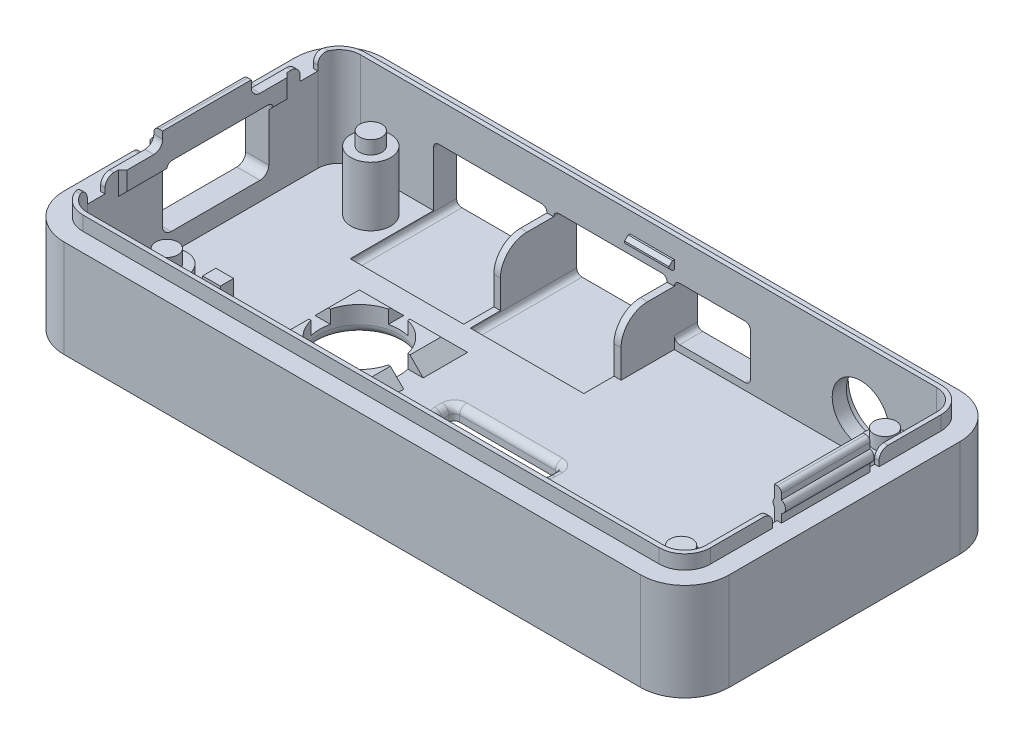
SolidWorks part; units mm, degrees
ref_plane "前视基准面" through (0, 0, 0) normal (0, 0, 1) x (1, 0, 0)
ref_plane "上视基准面" through (0, 0, 0) normal (0, 1, 0) x (1, 0, 0)
ref_plane "右视基准面" through (0, 0, 0) normal (1, 0, 0) x (0, 0, -1)
sketch "zero" plane through (0, 0, 0) normal (0, 1, 0) x (1, 0, 0)
  line L1 (-29.5, 15) -> (29.5, 15)
  line L2 (-32.5, 12) -> (-32.5, -12)
  line L3 (-29.5, -15) -> (29.5, -15)
  line L4 (32.5, 12) -> (32.5, -12)
  line L5 (-32.5, 15) -> (32.5, -15) construction
  line L6 (-32.5, -15) -> (32.5, 15) construction
  line L7 (-25.7, -15) -> (-14.5, -15)
  line L8 (-25.7, -15) -> (-25.7, -9.6569)
  line L9 (-25.7, -9.6569) -> (-14.5, -9.6569)
  line L10 (-14.5, -15) -> (-14.5, -9.6569)
  line L11 (5.2, -15) -> (12.7, -15)
  line L12 (5.2, -15) -> (5.2, -11)
  line L13 (5.2, -11) -> (12.7, -11)
  line L14 (12.7, -15) -> (12.7, -11)
  line L15 (17.8, -15) -> (25.3, -15)
  line L16 (17.8, -15) -> (17.8, -11)
  line L17 (17.8, -11) -> (25.3, -11)
  line L18 (25.3, -15) -> (25.3, -11)
  line L19 (-32.5, 7.7) -> (-19.5, 7.7)
  line L20 (-32.5, 7.7) -> (-32.5, -4.3)
  line L21 (-32.5, -4.3) -> (-19.5, -4.3)
  line L22 (-19.5, 7.7) -> (-19.5, -4.3)
  line L23 (-25.5, 14) -> (25.5, 14)
  line L24 (-25.5, 14) -> (-25.5, 8.8)
  line L25 (-25.5, 8.8) -> (25.5, 8.8)
  line L26 (25.5, 14) -> (25.5, 8.8)
  line L27 (-19.5, 7.2329) -> (-35.5, 7.2329)
  line L28 (-19.5, 7.2329) -> (-19.5, -3.7671)
  line L29 (-19.5, -3.7671) -> (-35.5, -3.7671)
  line L30 (-35.5, 7.2329) -> (-35.5, -3.7671)
  arc A0 (29.5, -15) -> (32.5, -12) centre (29.5, -12) ccw
  arc A1 (29.5, 15) -> (32.5, 12) centre (29.5, 12) cw
  arc A2 (-32.5, -12) -> (-29.5, -15) centre (-29.5, -12) ccw
  arc A3 (-29.5, 15) -> (-32.5, 12) centre (-29.5, 12) ccw
  circle A4 centre (-29, 11.4) radius 3
  circle A5 centre (-29, -11.5) radius 3
  circle A6 centre (29, 11.4) radius 3
  circle A7 centre (29, -11.5) radius 3
  circle A8 centre (-29, 11.4) radius 1.375
  circle A9 centre (-29, -11.5) radius 1.375
  circle A10 centre (29, -11.5) radius 1.375
  circle A11 centre (29, 11.4) radius 1.375
  point P0 (0, 0)
  dimension "D3" = 3
  dimension "D4" = 6
  dimension "D9" = 2.75
  dimension "D1" = 65
  dimension "D2" = 30
  dimension "D5" = 3.6
  dimension "D6" = 3.5
  dimension "D7" = 3.5
  dimension "D8" = 3.5
  dimension "D10" = 12
  dimension "D11" = 7.3
  dimension "D12" = 13
  dimension "D13" = 11.2
  dimension "D14" = 6.8
  dimension "D15" = 19.7
  dimension "D16" = 7.5
  dimension "D17" = 7.5
  dimension "D18" = 5.1
  dimension "D19" = 4
  dimension "D20" = 5.2
  dimension "D21" = 7
  dimension "D22" = 7
  dimension "D23" = 1
  dimension "D24" = 11
  dimension "D25" = 16
sketch "sugar" plane through (0, 0, 0) normal (0, 1, 0) x (1, 0, 0)
  line L1 (-29.5, 15) -> (29.5, 15)
  line L2 (-32.5, 12) -> (-32.5, -12)
  line L3 (-29.5, -15) -> (29.5, -15)
  line L4 (32.5, 12) -> (32.5, -12)
  line L5 (-32.5, 15) -> (32.5, -15) construction
  line L6 (-32.5, -15) -> (32.5, 15) construction
  line L7 (23.5, -11.5) -> (19.5, -11.5)
  line L8 (23.5, -11.5) -> (23.5, -13.9082)
  line L9 (23.5, -13.9082) -> (19.5, -13.9082)
  line L10 (19.5, -11.5) -> (19.5, -13.9082)
  line L11 (16, -11.0071) -> (8.5, -11.0071)
  line L12 (16, -11.0071) -> (16, -15)
  line L13 (16, -15) -> (8.5, -15)
  line L14 (8.5, -11.0071) -> (8.5, -15)
  line L15 (20.5, -13.9082) -> (22.5, -13.9082)
  line L16 (20.5, -13.9082) -> (20.5, -14.8173)
  line L17 (20.5, -14.8173) -> (22.5, -14.8173)
  line L18 (22.5, -13.9082) -> (22.5, -14.8173)
  arc A0 (29.5, 15) -> (32.5, 12) centre (29.5, 12) cw
  arc A1 (29.5, -15) -> (32.5, -12) centre (29.5, -12) ccw
  arc A2 (-32.5, -12) -> (-29.5, -15) centre (-29.5, -12) ccw
  arc A3 (-29.5, 15) -> (-32.5, 12) centre (-29.5, 12) ccw
  circle A4 centre (-29, 11.4) radius 3
  circle A5 centre (-29, 11.4) radius 1.375
  circle A6 centre (-29, -11.5) radius 3
  circle A7 centre (-29, -11.5) radius 1.375
  circle A8 centre (29, 11.4) radius 3
  circle A9 centre (29, 11.4) radius 1.375
  circle A10 centre (29, -11.5) radius 3
  circle A11 centre (29, -11.5) radius 1.375
  dimension "D3" = 3
  dimension "D1" = 65
  dimension "D2" = 30
  dimension "D4" = 9
  dimension "D5" = 4
  dimension "D6" = 3.5
  dimension "D7" = 7.5
  dimension "D8" = 2
  dimension "D9" = 1
sketch "case" plane through (0, 0, 0) normal (0, 1, 0) x (1, 0, 0)
  line L1 (-34.0422, 18) -> (30.9578, 18)
  line L2 (-39.0422, 13) -> (-39.0422, -13)
  line L3 (-34.0422, -18) -> (30.9578, -18)
  line L4 (35.9578, 13) -> (35.9578, -13)
  line L5 (-39.0422, 18) -> (35.9578, -18) construction
  line L6 (-39.0422, -18) -> (35.9578, 18) construction
  arc A0 (-39.0422, -13) -> (-34.0422, -18) centre (-34.0422, -13) ccw
  arc A1 (30.9578, -18) -> (35.9578, -13) centre (30.9578, -13) ccw
  arc A2 (30.9578, 18) -> (35.9578, 13) centre (30.9578, 13) cw
  arc A3 (-34.0422, 18) -> (-39.0422, 13) centre (-34.0422, 13) ccw
  point P0 (-1.5422, 0)
  point P3 (-1.5422, 0)
  dimension "D3" = 5
  dimension "D1" = 75
  dimension "D2" = 36
extrude "凸台-拉伸2" add sketch "case" along normal blind 11
sketch "草图2" plane through (0, 0, 0) normal (0, 1, 0) x (1, 0, 0)
  line L4 (-34.0422, -15.4) -> (30.9578, -15.4)
  line L5 (33.3578, -13) -> (33.3578, 13)
  line L6 (30.9578, 15.4) -> (-34.0422, 15.4)
  line L7 (-36.4422, 13) -> (-36.4422, -13)
  line L8 (33.8578, -13) -> (33.8578, 13)
  line L9 (30.9578, 15.9) -> (-34.0422, 15.9)
  line L10 (-36.9422, 13) -> (-36.9422, -13)
  line L11 (-34.0422, -15.9) -> (30.9578, -15.9)
  line L12 (33.8578, -13) -> (33.8578, 13)
  line L13 (30.9578, 15.9) -> (-34.0422, 15.9)
  line L14 (-36.9422, 13) -> (-36.9422, -13)
  line L15 (-34.0422, -15.9) -> (30.9578, -15.9)
  arc A4 (30.9578, -15.4) -> (33.3578, -13) centre (30.9578, -13) ccw
  arc A5 (33.3578, 13) -> (30.9578, 15.4) centre (30.9578, 13) ccw
  arc A6 (-34.0422, 15.4) -> (-36.4422, 13) centre (-34.0422, 13) ccw
  arc A7 (-36.4422, -13) -> (-34.0422, -15.4) centre (-34.0422, -13) ccw
  arc A8 (30.9578, -15.9) -> (33.8578, -13) centre (30.9578, -13) ccw
  arc A9 (33.8578, 13) -> (30.9578, 15.9) centre (30.9578, 13) ccw
  arc A10 (-34.0422, 15.9) -> (-36.9422, 13) centre (-34.0422, 13) ccw
  arc A11 (-36.9422, -13) -> (-34.0422, -15.9) centre (-34.0422, -13) ccw
  arc A12 (30.9578, -15.9) -> (33.8578, -13) centre (30.9578, -13) ccw
  arc A13 (33.8578, 13) -> (30.9578, 15.9) centre (30.9578, 13) ccw
  arc A14 (-34.0422, 15.9) -> (-36.9422, 13) centre (-34.0422, 13) ccw
  arc A15 (-36.9422, -13) -> (-34.0422, -15.9) centre (-34.0422, -13) ccw
  dimension "D1" = 2.1
  dimension "D2" = 0.5
ref_plane "基准面1" through (0, 11, 0) normal (0, 1, 0) x (1, 0, 0)
sketch "草图3" plane through (0, 11, 0) normal (0, 1, 0) x (1, 0, 0)
  line L4 (-34.0422, -15.4) -> (30.9578, -15.4)
  line L5 (33.3578, -13) -> (33.3578, 13)
  line L6 (30.9578, 15.4) -> (-34.0422, 15.4)
  line L7 (-36.4422, 13) -> (-36.4422, -13)
  line L8 (-34.0422, -15.4) -> (30.9578, -15.4)
  line L9 (33.3578, -13) -> (33.3578, 13)
  line L10 (30.9578, 15.4) -> (-34.0422, 15.4)
  line L11 (-36.4422, 13) -> (-36.4422, -13)
  line L12 (-36.9422, 13) -> (-36.9422, -13)
  line L13 (-34.0422, -15.9) -> (30.9578, -15.9)
  line L14 (33.8578, -13) -> (33.8578, 13)
  line L15 (30.9578, 15.9) -> (-34.0422, 15.9)
  line L16 (-36.9422, 13) -> (-36.9422, -13)
  line L17 (-34.0422, -15.9) -> (30.9578, -15.9)
  line L18 (33.8578, -13) -> (33.8578, 13)
  line L19 (30.9578, 15.9) -> (-34.0422, 15.9)
  arc A4 (30.9578, -15.4) -> (33.3578, -13) centre (30.9578, -13) ccw
  arc A5 (33.3578, 13) -> (30.9578, 15.4) centre (30.9578, 13) ccw
  arc A6 (-34.0422, 15.4) -> (-36.4422, 13) centre (-34.0422, 13) ccw
  arc A7 (-36.4422, -13) -> (-34.0422, -15.4) centre (-34.0422, -13) ccw
  arc A8 (30.9578, -15.4) -> (33.3578, -13) centre (30.9578, -13) ccw
  arc A9 (33.3578, 13) -> (30.9578, 15.4) centre (30.9578, 13) ccw
  arc A10 (-34.0422, 15.4) -> (-36.4422, 13) centre (-34.0422, 13) ccw
  arc A11 (-36.4422, -13) -> (-34.0422, -15.4) centre (-34.0422, -13) ccw
  arc A12 (-36.9422, -13) -> (-34.0422, -15.9) centre (-34.0422, -13) ccw
  arc A13 (30.9578, -15.9) -> (33.8578, -13) centre (30.9578, -13) ccw
  arc A14 (33.8578, 13) -> (30.9578, 15.9) centre (30.9578, 13) ccw
  arc A15 (-34.0422, 15.9) -> (-36.9422, 13) centre (-34.0422, 13) ccw
  arc A16 (-36.9422, -13) -> (-34.0422, -15.9) centre (-34.0422, -13) ccw
  arc A17 (30.9578, -15.9) -> (33.8578, -13) centre (30.9578, -13) ccw
  arc A18 (33.8578, 13) -> (30.9578, 15.9) centre (30.9578, 13) ccw
  arc A19 (-34.0422, 15.9) -> (-36.9422, 13) centre (-34.0422, 13) ccw
  dimension "D1" = 0
  dimension "D2" = 0
extrude "凸台-拉伸4" add sketch "草图3" along normal blind 1.6
sketch "草图5" plane through (0, 11, 0) normal (0, 1, 0) x (1, 0, 0)
  line L0 (33.3578, -13) -> (33.3578, 13) construction
  line L1 (33.0578, 5) -> (33.3578, 5)
  line L2 (33.0578, 5) -> (33.0578, -5)
  line L3 (33.0578, -5) -> (33.3578, -5)
  line L4 (33.3578, 5) -> (33.3578, -5)
  line L5 (33.0578, 5) -> (33.3578, -5) construction
  line L6 (33.0578, -5) -> (33.3578, 5) construction
  point P0 (33.2078, 0)
  dimension "D2" = 10
  dimension "D3" = 0.3
  dimension "D4" = 0
ref_plane "基准面3" through (33.8578, 0, 0) normal (1, 0, 0) x (0, 0, -1)
ref_plane "基准面7" through (-36.9422, 0, 0) normal (-1, 0, 0) x (0, 0, 1)
ref_plane "基准面8" through (0, 0, 0) normal (0, -1, 0) x (-1, 0, 0)
sketch "草图14" plane through (0, 11, 0) normal (0, 1, 0) x (1, 0, 0)
  line L4 (-34.0422, -15.4) -> (30.9578, -15.4)
  line L5 (33.3578, -13) -> (33.3578, 13)
  line L6 (30.9578, 15.4) -> (-34.0422, 15.4)
  line L7 (-36.4422, 13) -> (-36.4422, -13)
  line L8 (-34.0422, -15.4) -> (30.9578, -15.4)
  line L9 (33.3578, -13) -> (33.3578, 13)
  line L10 (30.9578, 15.4) -> (-34.0422, 15.4)
  line L11 (-36.4422, 13) -> (-36.4422, -13)
  arc A4 (30.9578, -15.4) -> (33.3578, -13) centre (30.9578, -13) ccw
  arc A5 (33.3578, 13) -> (30.9578, 15.4) centre (30.9578, 13) ccw
  arc A6 (-34.0422, 15.4) -> (-36.4422, 13) centre (-34.0422, 13) ccw
  arc A7 (-36.4422, -13) -> (-34.0422, -15.4) centre (-34.0422, -13) ccw
  arc A8 (30.9578, -15.4) -> (33.3578, -13) centre (30.9578, -13) ccw
  arc A9 (33.3578, 13) -> (30.9578, 15.4) centre (30.9578, 13) ccw
  arc A10 (-34.0422, 15.4) -> (-36.4422, 13) centre (-34.0422, 13) ccw
  arc A11 (-36.4422, -13) -> (-34.0422, -15.4) centre (-34.0422, -13) ccw
  dimension "D1" = 0
extrude "切除-拉伸2" cut sketch "草图14" against normal blind 9.5
extrude "凸台-拉伸12" add sketch "草图5" against normal blind 2 and the other way blind 1.6
sketch "草图15" plane through (0, 1.5, 0) normal (0, 1, 0) x (1, 0, 0)
  line L1 (35.9578, -13) -> (35.9578, 13) construction
  line L5 (-39.0422, 13) -> (-39.0422, -13) construction
  line L6 (-34.0422, -18) -> (30.9578, -18) construction
  line L7 (30.9578, 18) -> (-34.0422, 18) construction
  circle A0 centre (29.0603, -11.5295) radius 2.25
  circle A1 centre (-28.9397, -11.5295) radius 2.25
  circle A2 centre (29.0603, 11.4705) radius 2.25
  circle A3 centre (-28.9397, 11.4705) radius 2.25
  dimension "D1" = 4.5
  dimension "D2" = 6.8975
  dimension "D3" = 10.1025
  dimension "D4" = 6.4705
  dimension "D5" = 6.5295
extrude "凸台-拉伸13" add sketch "草图15" along normal blind 6.7
sketch "草图16" plane through (0, 8.2, 0) normal (0, 1, 0) x (1, 0, 0)
  circle A0 centre (29.0603, -11.5295) radius 1.25
  circle A1 centre (29.0603, 11.4705) radius 1.25
  circle A2 centre (-28.9397, -11.5295) radius 1.25
  circle A3 centre (-28.9397, 11.4705) radius 1.25
  dimension "D1" = 2.5
extrude "凸台-拉伸14" add sketch "草图16" along normal blind 1.5
sketch "草图17" plane through (0, 12.6, 0) normal (0, 1, 0) x (1, 0, 0)
  line L0 (33.3578, -13) -> (33.3578, -5) construction
  line L1 (33.3578, -5) -> (33.8578, -5)
  line L2 (33.3578, -5) -> (33.3578, -6)
  line L3 (33.3578, -6) -> (33.8578, -6)
  line L4 (33.8578, -5) -> (33.8578, -6)
  line L5 (33.3578, -13) -> (33.3578, 13) construction
  line L6 (33.8578, -13) -> (33.8578, 13) construction
  line L8 (33.3578, 5) -> (33.8578, 5)
  line L9 (33.3578, 5) -> (33.3578, 6)
  line L10 (33.3578, 6) -> (33.8578, 6)
  line L11 (33.8578, 5) -> (33.8578, 6)
  dimension "D1" = 1
  dimension "D2" = 1
extrude "切除-拉伸3" cut sketch "草图17" against normal blind 1.6
sketch "草图19" plane through (0, 12.6, 0) normal (0, 1, 0) x (1, 0, 0)
  line L0 (33.0578, 5) -> (33.0578, -5) construction
  line L1 (33.8578, -5) -> (33.0578, -5)
  line L2 (33.8578, -5) -> (33.8578, 5)
  line L3 (33.8578, 5) -> (33.0578, 5)
  line L4 (33.0578, -5) -> (33.0578, 5)
extrude "凸台-拉伸15" add sketch "草图19" along normal blind 1.8
sketch "草图20" plane through (0, 0, -5) normal (0, 0, -1) x (-1, 0, 0)
  line L0 (-30.9578, 11) -> (-35.9578, 11) construction
  line L3 (-33.8578, 11) -> (-33.8578, 14.4) construction
  circle A0 centre (-33.6078, 12.6) radius 0.7
  dimension "D1" = 1.4
  dimension "D2" = 1.6
  dimension "D3" = 0.25
extrude "凸台-拉伸16" add sketch "草图20" against normal blind 10
fillet "圆角4" radius 0.5 1 edges at (33.8578, 14.4, 0)
sketch "草图37" plane through (0, 0, -15.4) normal (0, 0, 1) x (1, 0, 0)
  line L0 (-34.0422, 12.6) -> (30.9578, 12.6) construction
  line L1 (-3.6422, 10.3) -> (1.3578, 10.3)
  line L2 (-3.6422, 10.3) -> (-3.6422, 9.3)
  line L3 (-3.6422, 9.3) -> (1.3578, 9.3)
  line L4 (1.3578, 10.3) -> (1.3578, 9.3)
  line L5 (33.3578, 12.6) -> (33.3578, 1.5) construction
  dimension "D1" = 5
  dimension "D2" = 1
  dimension "D3" = 2.3
  dimension "D4" = 32
extrude "凸台-拉伸17" add sketch "草图37" along normal blind 0.6
chamfer "倒角1" distance 0.4 angle 45 2 edges at (-1.1422, 9.3, -14.8) (-1.1422, 10.3, -14.8)
sketch "草图38" plane through (0, 0, 15.4) normal (0, 0, -1) x (-1, 0, 0)
  line L0 (-30.9578, 12.6) -> (34.0422, 12.6) construction
  line L1 (4.5422, 10.4) -> (-1.4578, 10.4)
  line L2 (4.5422, 10.4) -> (4.5422, 9.4)
  line L3 (4.5422, 9.4) -> (-1.4578, 9.4)
  line L4 (-1.4578, 10.4) -> (-1.4578, 9.4)
  point P6 (1.5422, 10.4)
  point P7 (1.5422, 12.6)
  dimension "D1" = 1
  dimension "D2" = 6
  dimension "D3" = 2.2
extrude "凸台-拉伸18" add sketch "草图38" along normal blind 0.7
chamfer "倒角2" distance 0.4 angle 45 2 edges at (-1.5422, 9.4, 14.7) (-1.5422, 10.4, 14.7)
sketch "草图39" plane through (0, 0, -18) normal (0, 0, -1) x (-1, 0, 0)
  line L0 (-30.9578, 0) -> (34.0422, 0) construction
  line L1 (-35.9578, 11) -> (-35.9578, 0) construction
  circle A0 centre (-22.3721, 5.7789) radius 4
  dimension "D1" = 5.7789
  dimension "D3" = 8
  dimension "D2" = 13.5857
extrude "切除-拉伸4" cut sketch "草图39" against normal blind 1
sketch "草图41" plane through (0, 0, -18) normal (0, 0, -1) x (-1, 0, 0)
  line L0 (-30.9578, 0) -> (34.0422, 0) construction
  line L1 (-9.9578, 2.2789) -> (-1.3578, 2.2789)
  line L2 (-9.9578, 2.2789) -> (-9.9578, 8.2789)
  line L3 (-9.9578, 8.2789) -> (-1.3578, 8.2789)
  line L4 (-1.3578, 2.2789) -> (-1.3578, 8.2789)
  line L5 (-0.5578, 0.7789) -> (12.2422, 0.7789)
  line L6 (-0.5578, 0.7789) -> (-0.5578, 8.2789)
  line L7 (-0.5578, 8.2789) -> (12.2422, 8.2789)
  line L8 (12.2422, 0.7789) -> (12.2422, 8.2789)
  line L9 (12.9922, 0.7789) -> (25.7922, 0.7789)
  line L10 (12.9922, 0.7789) -> (12.9922, 8.2789)
  line L11 (12.9922, 8.2789) -> (25.7922, 8.2789)
  line L12 (25.7922, 0.7789) -> (25.7922, 8.2789)
  line L13 (-35.9578, 11) -> (-35.9578, 0) construction
  point P14 (0, 0)
  point P15 (0, 0)
  dimension "D1" = 8.2789
  dimension "D2" = 26
  dimension "D3" = 8.6
  dimension "D4" = 6
  dimension "D5" = 0.8
  dimension "D6" = 7.5
  dimension "D7" = 12.8
  dimension "D8" = 0.75
  dimension "D9" = 12.8
extrude "切除-拉伸5" cut sketch "草图41" against normal blind 12
fillet "圆角5" radius 0.6 14 edges at (-19.3922, 0.7789, -6) (-5.8422, 0.7789, -6) (1.3578, 2.2789, -16.7) (9.9578, 2.2789, -16.7) (9.9578, 8.2789, -16.7) (1.3578, 8.2789, -16.7) (0.5578, 8.2789, -16.7) (-12.2422, 8.2789, -16.7) (-12.9922, 8.2789, -16.7) (-25.7922, 8.2789, -16.7) (-12.2422, 0.7789, -12) (0.5578, 0.7789, -12) (-12.9922, 0.7789, -12) (-25.7922, 0.7789, -12)
sketch "草图42" plane through (0, 0, -17) normal (0, 0, -1) x (-1, 0, 0)
  circle A0 centre (-22.3721, 5.7789) radius 3.2
extrude "切除-拉伸6" cut sketch "草图42" against normal blind 1.6
sketch "草图44" plane through (-39.0422, 0, 0) normal (-1, 0, 0) x (0, 0, 1)
  line L0 (-18, 11) -> (-18, 0) construction
  line L1 (-7.4705, 3.6) -> (4.5295, 3.6)
  line L2 (-7.4705, 3.6) -> (-7.4705, 11)
  line L3 (-7.4705, 11) -> (4.5295, 11)
  line L4 (4.5295, 3.6) -> (4.5295, 11)
  line L5 (-7.4705, 3.6) -> (4.5295, 11) construction
  line L6 (-7.4705, 11) -> (4.5295, 3.6) construction
  line L7 (-13, 0) -> (13, 0) construction
  point P0 (-1.4705, 7.3)
  dimension "D1" = 12
  dimension "D2" = 16.5295
  dimension "D3" = 7.3
  dimension "D4" = 7.4
extrude "切除-拉伸8" cut sketch "草图44" against normal up to next
sketch "草图46" plane through (-36.4422, 0, 0) normal (1, 0, 0) x (0, 0, -1)
  line L0 (13, 12.6) -> (-13, 12.6) construction
  line L1 (-10, 12.6) -> (10, 12.6)
  line L2 (-10, 12.6) -> (-10, 11)
  line L3 (-10, 11) -> (10, 11)
  line L4 (10, 12.6) -> (10, 11)
  line L6 (-18, 11) -> (-18, 0) construction
  point P10 (0, 0)
  dimension "D1" = 8
  dimension "D2" = 8
extrude "凸台-拉伸19" add sketch "草图46" along normal blind 0.5
chamfer "倒角3" distance 1 angle 45 2 edges at (-35.9422, 11.8, -10) (-35.9422, 11.8, 10)
chamfer "倒角4" distance 1 angle 45 2 edges at (-36.4422, 11, -8.4853) (-36.4422, 11, 7.0147)
fillet "圆角7" radius 1 2 edges at (-37.7422, 3.6, 4.5295) (-37.7422, 3.6, -7.4705)
sketch "草图47" plane through (0, 0, -15.4) normal (0, 0, 1) x (1, 0, 0)
  line L1 (-12.9922, 1.5) -> (-12.2422, 1.5)
  line L2 (-12.9922, 1.5) -> (-12.9922, 7.6789)
  line L3 (-12.9922, 7.6789) -> (-12.2422, 7.6789)
  line L4 (-12.2422, 1.5) -> (-12.2422, 7.6789)
  line L5 (0.5578, 1.5) -> (1.3578, 1.5)
  line L6 (0.5578, 1.5) -> (0.5578, 7.6789)
  line L7 (0.5578, 7.6789) -> (1.3578, 7.6789)
  line L8 (1.3578, 1.5) -> (1.3578, 7.6789)
extrude "凸台-拉伸20" add sketch "草图47" along normal blind 6
fillet "圆角8" radius 3 2 edges at (0.9578, 7.6789, -9.4) (-12.6172, 7.6789, -9.4)
sketch "草图48" plane through (0, 12.6, 0) normal (0, 1, 0) x (1, 0, 0)
  line L0 (-35.9422, 9) -> (-35.9422, -9) construction
  line L1 (-35.9422, -5) -> (-36.9422, -5)
  line L2 (-35.9422, -5) -> (-35.9422, 5)
  line L3 (-35.9422, 5) -> (-36.9422, 5)
  line L4 (-36.9422, -5) -> (-36.9422, 5)
  line L5 (-36.9422, 13) -> (-36.9422, -13) construction
  point P8 (0, 0)
  point P10 (0, 0)
  point P11 (0, 0)
  point P13 (0, 0)
extrude "凸台-拉伸21" add sketch "草图48" along normal blind 1.8
sketch "草图49" plane through (0, 0, 5) normal (0, 0, 1) x (1, 0, 0)
  line L0 (-34.0422, 11) -> (-39.0422, 11) construction
  line L1 (-36.9422, 14.4) -> (-36.9422, 12.6) construction
  circle A0 centre (-36.6922, 12.6) radius 0.7
  dimension "D1" = 1.4
  dimension "D2" = 1.6
  dimension "D3" = 0.25
extrude "凸台-拉伸22" add sketch "草图49" against normal blind 10
sketch "草图50" plane through (0, 12.6, 0) normal (0, 1, 0) x (1, 0, 0)
  line L0 (-36.4422, 13) -> (-36.4422, 9.5) construction
  line L1 (-36.4422, 13) -> (-36.9422, 13)
  line L2 (-36.4422, 13) -> (-36.4422, 11)
  line L3 (-36.4422, 11) -> (-36.9422, 11)
  line L4 (-36.9422, 13) -> (-36.9422, 11)
  line L5 (-36.9422, 13) -> (-36.9422, 5) construction
  line L6 (-36.4422, -9.5) -> (-36.4422, -13) construction
  line L7 (-36.4422, -11) -> (-36.9422, -11)
  line L8 (-36.4422, -11) -> (-36.4422, -13)
  line L9 (-36.4422, -13) -> (-36.9422, -13)
  line L10 (-36.9422, -11) -> (-36.9422, -13)
  line L11 (-36.9422, -5) -> (-36.9422, -13) construction
  line L12 (30.9578, 18) -> (-34.0422, 18) construction
  line L13 (-34.0422, -18) -> (30.9578, -18) construction
  dimension "D1" = 2
  dimension "D2" = 2
  dimension "D3" = 5
  dimension "D4" = 5
extrude "切除-拉伸10" cut sketch "草图50" against normal blind 1.6
fillet "圆角9" radius 1 6 edges at (33.6078, 12.6, 6) (33.6078, 12.6, -6) (-36.6922, 12.6, -13) (-36.6922, 12.6, -11) (-36.6922, 12.6, 11) (-36.6922, 12.6, 13)
fillet "圆角10" radius 0.6 1 edges at (-36.9422, 14.4, 0)
fillet "圆角11" radius 0.6 2 edges at (-36.4422, 11, -7.4705) (-36.4422, 11, 4.5295)
fillet "圆角12" radius 0.6 2 edges at (-37.9922, 11, 4.5295) (-37.9922, 11, -7.4705)
sketch "草图51" plane through (0, 0, 0) normal (0, -1, 0) x (1, 0, 0)
  line L0 (35.9578, 13) -> (35.9578, -13) construction
  line L1 (6.2578, 2.3) -> (-5.7422, 2.3)
  line L2 (6.2578, 2.3) -> (6.2578, 4.3)
  line L3 (6.2578, 4.3) -> (-5.7422, 4.3)
  line L4 (-5.7422, 2.3) -> (-5.7422, 4.3)
  line L5 (30.9578, -18) -> (-34.0422, -18) construction
  dimension "D1" = 2
  dimension "D2" = 12
  dimension "D3" = 29.7
  dimension "D4" = 20.3
extrude "切除-拉伸11" cut sketch "草图51" against normal blind 1.5
fillet "圆角13" radius 0.6 4 edges at (-5.7422, 0.75, 4.3) (-5.7422, 0.75, 2.3) (6.2578, 0.75, 4.3) (6.2578, 0.75, 2.3)
sketch "草图52" plane through (0, 1.5, 0) normal (0, 1, 0) x (1, 0, 0)
  line L0 (-11.5279, -7.2295) -> (-20.7279, -7.2295)
  line L5 (-20.7279, -7.2295) -> (-20.7279, 1.9705)
  line L6 (-11.5279, 1.9705) -> (-20.7279, 1.9705)
  line L7 (-11.5279, -7.2295) -> (-11.5279, 1.9705)
  line L8 (-39.0422, -5.1295) -> (-39.0422, -13) construction
  line L9 (-34.0422, -18) -> (30.9578, -18) construction
  point P6 (0, 0)
  point P7 (0, 0)
  point P8 (0, 0)
  point P9 (0, 0)
  point P10 (0, 0)
  dimension "D1" = 9.2
  dimension "D2" = 9.2
  dimension "D3" = 18.3143
  dimension "D4" = 10.7705
extrude "凸台-拉伸23" add sketch "草图52" along normal blind 1.5
chamfer "倒角5" distance 1.5 angle 45 4 edges at (-16.1279, 1.5, -1.9705) (-11.5279, 1.5, 2.6295) (-16.1279, 1.5, 7.2295) (-20.7279, 1.5, 2.6295)
sketch "草图53" plane through (0, 0, 0) normal (0, -1, 0) x (1, 0, 0)
  line L1 (30.9578, -18) -> (-34.0422, -18) construction
  line L2 (-39.0422, -13) -> (-39.0422, 13) construction
  circle A0 centre (-16.1279, 2.6295) radius 4.5
  point P4 (0, 0)
  dimension "D1" = 9
  dimension "D2" = 20.6295
  dimension "D3" = 22.9143
extrude "切除-拉伸12" cut sketch "草图53" against normal up to next
fillet "圆角14" radius 1 1 edges at (-16.1279, 0, -1.8705)
sketch "草图55" plane through (0, 3, 0) normal (0, 1, 0) x (1, 0, 0)
  line L1 (-10.0279, -3.7295) -> (-22.2279, -3.7295)
  line L2 (-10.0279, -3.7295) -> (-10.0279, -1.5295)
  line L3 (-10.0279, -1.5295) -> (-22.2279, -1.5295)
  line L4 (-22.2279, -3.7295) -> (-22.2279, -1.5295)
  line L5 (-10.0279, -3.7295) -> (-22.2279, -1.5295) construction
  line L6 (-10.0279, -1.5295) -> (-22.2279, -3.7295) construction
  circle A0 centre (-16.1279, -2.6295) radius 4.5 construction
  point P0 (-16.1279, -2.6295)
  point P5 (0, 0)
  dimension "D1" = 12.2
  dimension "D2" = 2.2
extrude "切除-拉伸13" cut sketch "草图55" against normal blind 1.5
sketch "草图56" plane through (0, 3, 0) normal (0, 1, 0) x (1, 0, 0)
  line L1 (-15.0279, -8.7295) -> (-17.2279, -8.7295)
  line L2 (-15.0279, -8.7295) -> (-15.0279, 3.4705)
  line L3 (-15.0279, 3.4705) -> (-17.2279, 3.4705)
  line L4 (-17.2279, -8.7295) -> (-17.2279, 3.4705)
  line L5 (-15.0279, -8.7295) -> (-17.2279, 3.4705) construction
  line L6 (-15.0279, 3.4705) -> (-17.2279, -8.7295) construction
  arc A0 (-11.7644, -3.7295) -> (-11.7644, -1.5295) centre (-16.1279, -2.6295) ccw construction
  point P0 (-16.1279, -2.6295)
  point P5 (0, 0)
  point P6 (0, 0)
  point P7 (0, 0)
  dimension "D1" = 12.2
  dimension "D2" = 2.2
extrude "切除-拉伸14" cut sketch "草图56" against normal blind 1.5
sketch "草图62" plane through (0, 0, 0) normal (0, -1, 0) x (1, 0, 0)
  line L54 (24.7651, -13.4168) -> (25.178, -13.6486)
  line L55 (25.178, -13.6486) -> (27.3204, -14.8522)
  line L56 (27.3204, -14.8522) -> (27.7334, -15.0868)
  line L57 (28.5939, -15.077) -> (29.0014, -14.8329)
  line L58 (29.0014, -14.8329) -> (31.1156, -13.5806)
  line L60 (31.1156, -13.5806) -> (31.5232, -13.3394)
  line L61 (31.9449, -12.5909) -> (31.9059, -9.1833)
  line L62 (31.4672, -8.4446) -> (31.0542, -8.2128)
  line L63 (31.0542, -8.2128) -> (28.9118, -7.0092)
  line L65 (28.9118, -7.0092) -> (28.4988, -6.7746)
  line L66 (27.6383, -6.7844) -> (27.2308, -7.0284)
  line L67 (27.2308, -7.0284) -> (25.1166, -8.2808)
  line L68 (25.1166, -8.2808) -> (24.709, -8.522)
  line L69 (24.2873, -9.2705) -> (24.3263, -12.6781)
  line L70 (30.9723, -13.0066) -> (28.3571, -14.5582)
  line L73 (27.9554, -14.5628) -> (25.3196, -13.0685)
  line L74 (25.3127, -12.7181) -> (27.8396, -11.1675)
  line L75 (27.0208, -8.5981) -> (27.3152, -8.4295)
  line L76 (27.3432, -8.3807) -> (27.3334, -7.5259)
  line L77 (27.3613, -7.4772) -> (27.9105, -7.1575)
  line L78 (27.9937, -7.2049) -> (28.0239, -9.8432)
  line L79 (27.996, -9.892) -> (27.0618, -10.4356)
  line L80 (25.0712, -8.7971) -> (25.6147, -8.4803)
  line L81 (25.6979, -8.5278) -> (25.7123, -9.7842)
  line L82 (25.6843, -9.833) -> (25.1408, -10.147)
  line L83 (25.0576, -10.0995) -> (25.0433, -8.8459)
  line L84 (27.0608, -9.1049) -> (27.3214, -8.9708)
  line L85 (27.3506, -9.0303) -> (27.3583, -9.7027)
  line L86 (27.3304, -9.7514) -> (27.0869, -9.891)
  line L129 (27.3214, -8.9708) -> (27.3152, -8.4295)
  line L130 (27.3506, -9.0303) -> (27.3432, -8.3807)
  spline S0 degree 3 poles (27.7334, -15.0868) (27.8682, -15.1594) (28.0168, -15.1976) (28.1649, -15.1959) knots 3 3 3 3 4 4 4 4
  spline S1 degree 3 poles (28.1649, -15.1959) (28.3131, -15.1942) (28.4608, -15.1526) (28.5939, -15.077) knots 4 4 4 4 5 5 5 5
  spline S2 degree 3 poles (31.5232, -13.3394) (31.7864, -13.1825) (31.9484, -12.8957) (31.9449, -12.5909) knots 8 8 8 8 9 9 9 9
  spline S3 degree 3 poles (31.9059, -9.1833) (31.9024, -8.8756) (31.7339, -8.5954) (31.4672, -8.4446) knots 10 10 10 10 11 11 11 11
  spline S4 degree 3 poles (28.4988, -6.7746) (28.364, -6.6992) (28.2154, -6.6638) (28.0673, -6.6655) knots 14 14 14 14 15 15 15 15
  spline S5 degree 3 poles (28.0673, -6.6655) (27.9191, -6.6672) (27.7714, -6.706) (27.6383, -6.7844) knots 15 15 15 15 16 16 16 16
  spline S6 degree 3 poles (24.709, -8.522) (24.4429, -8.6789) (24.2838, -8.9628) (24.2873, -9.2705) knots 19 19 19 19 20 20 20 20
  spline S7 degree 3 poles (24.3263, -12.6781) (24.3298, -12.983) (24.4955, -13.266) (24.7651, -13.4168) knots 21 21 21 21 22 22 22 22
  spline S8 degree 2 poles (28.3952, -11.1612) (30.9878, -12.6189) (30.9935, -12.6217) knots 0 0 0 1 1 1
  spline S9 degree 3 poles (30.9935, -12.6217) (31.1285, -12.717) (31.1167, -12.9223) (30.9723, -13.0066) knots 1 1 1 1 2 2 2 2
  spline S10 degree 3 poles (28.3571, -14.5582) (28.2354, -14.6309) (28.0815, -14.6326) (27.9554, -14.5628) knots 3 3 3 3 4 4 4 4
  spline S11 degree 3 poles (25.3196, -13.0685) (25.1848, -12.9931) (25.1797, -12.7994) (25.3127, -12.7181) knots 5 5 5 5 6 6 6 6
  spline S12 degree 3 poles (27.8396, -11.1675) (28.0094, -11.0658) (28.2231, -11.0634) (28.3952, -11.1612) knots 7 7 7 7 8 8 8 8
  spline S13 degree 3 poles (27.3334, -7.5259) (27.3332, -7.506) (27.3415, -7.4888) (27.3613, -7.4772) knots 3 3 3 3 4 4 4 4
  spline S14 degree 3 poles (27.9105, -7.1575) (27.9473, -7.1371) (27.9932, -7.1622) (27.9937, -7.2049) knots 5 5 5 5 6 6 6 6
  spline S15 degree 3 poles (28.0239, -9.8432) (28.0241, -9.8632) (28.0158, -9.8832) (27.996, -9.892) knots 7 7 7 7 8 8 8 8
  spline S16 degree 3 poles (27.0618, -10.4356) (26.456, -10.7873) (25.9526, -10.8614) (25.9447, -10.1776) knots 9 9 9 9 10 10 10 10
  spline S17 degree 3 poles (25.9447, -10.1776) (25.9372, -9.5195) (26.4405, -8.9353) (27.0208, -8.5981) knots 10 10 10 10 11 11 11 11
  spline S18 degree 3 poles (25.0433, -8.8459) (25.043, -8.8259) (25.0542, -8.8058) (25.0712, -8.7971) knots 0 0 0 0 1 1 1 1
  spline S19 degree 3 poles (25.6147, -8.4803) (25.6515, -8.4599) (25.6974, -8.485) (25.6979, -8.5278) knots 2 2 2 2 3 3 3 3
  spline S20 degree 3 poles (25.7123, -9.7842) (25.7125, -9.8042) (25.7013, -9.8214) (25.6843, -9.833) knots 4 4 4 4 5 5 5 5
  spline S21 degree 3 poles (25.1408, -10.147) (25.104, -10.1673) (25.0581, -10.1422) (25.0576, -10.0995) knots 6 6 6 6 7 7 7 7
  spline S22 degree 3 poles (25.3954, -10.979) (25.1774, -11.1068) (25.0201, -11.0545) (25.0178, -10.8551) (25.0156, -10.6585) (25.1696, -10.4259) (25.3876, -10.3009) knots 2 2 2 2 3 3 3 4 4 4 4
  spline S23 degree 3 poles (25.3876, -10.3009) (25.6084, -10.1701) (25.7657, -10.2224) (25.7679, -10.419) (25.7703, -10.6213) (25.6162, -10.8511) (25.3954, -10.979) knots 0 0 0 0 1 1 1 2 2 2 2
  spline S24 degree 3 poles (26.5901, -9.8027) (26.587, -9.532) (26.7381, -9.2909) (27.0608, -9.1049) knots 0 0 0 0 1 1 1 1
  spline S25 degree 3 poles (27.3583, -9.7027) (27.3586, -9.7226) (27.3474, -9.7427) (27.3304, -9.7514) knots 4 4 4 4 5 5 5 5
  spline S26 degree 3 poles (27.0869, -9.891) (26.7699, -10.077) (26.5933, -10.0819) (26.5901, -9.8027) knots 6 6 6 6 7 7 7 7
  point P0 (30.8413, -12.8455)
extrude "切除-拉伸15" cut sketch "草图62" against normal blind 0.5
fillet "圆角15" radius 0.8 8 edges at (-5.5665, 1.5, 2.4757) (-5.7422, 1.5, 3.3) (-5.5665, 1.5, 4.1243) (0.2578, 1.5, 4.3) (6.0821, 1.5, 4.1243) (6.2578, 1.5, 3.3) (6.0821, 1.5, 2.4757) (0.2578, 1.5, 2.3)
fillet "圆角17" radius 1 2 edges at (-36.4422, 12.6, 5) (-36.4422, 12.6, -5)
sketch "草图63" plane through (0, 1.5, 0) normal (0, 1, 0) x (1, 0, 0)
  line L0 (-25.7922, 15.4) -> (-34.0422, 15.4) construction
  line L1 (-30.4422, -4.5) -> (-28.4422, -4.5)
  line L2 (-30.4422, -4.5) -> (-30.4422, -6)
  line L3 (-30.4422, -6) -> (-28.4422, -6)
  line L4 (-28.4422, -4.5) -> (-28.4422, -6)
  line L5 (-36.4422, 13) -> (-36.4422, -13) construction
  dimension "D1" = 2
  dimension "D2" = 1.5
  dimension "D3" = 19.9
  dimension "D4" = 6
extrude "凸台-拉伸24" add sketch "草图63" along normal blind 2
